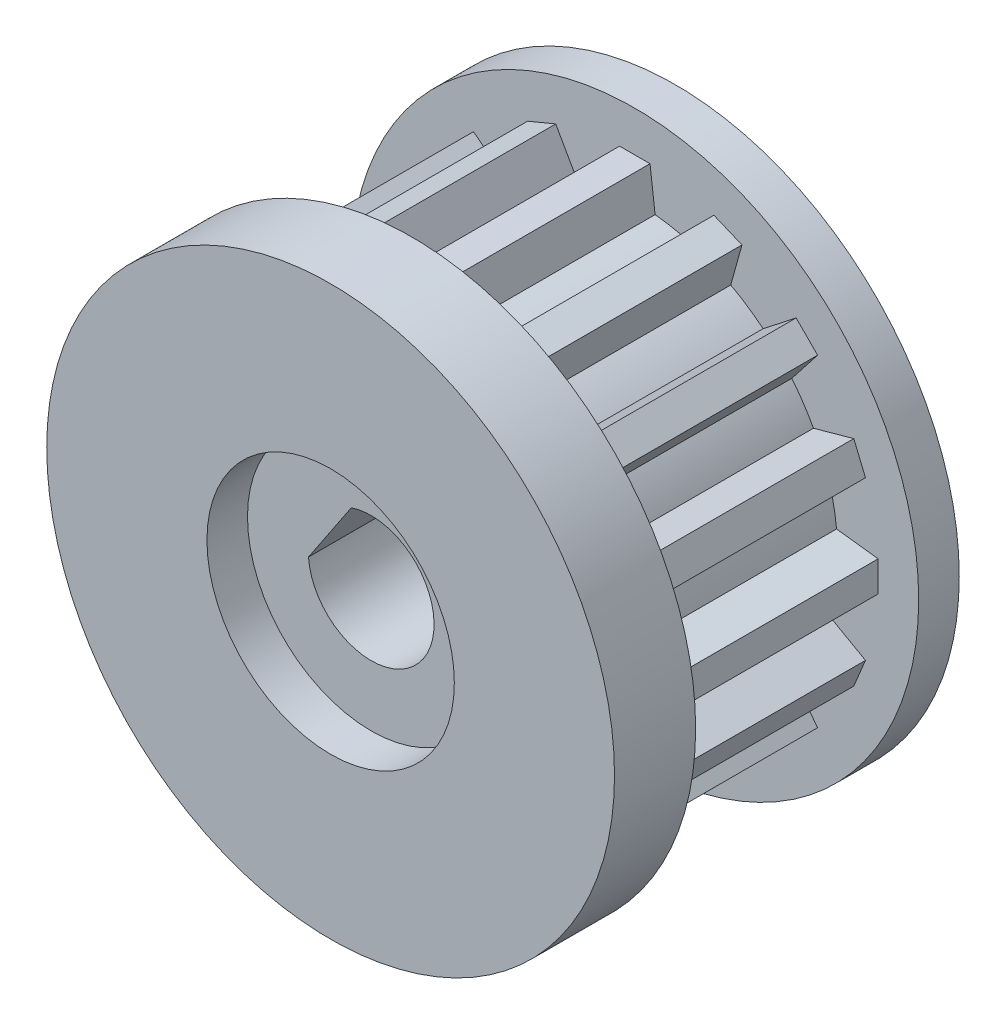
SolidWorks part; units mm, degrees
ref_plane "正面" through (0, 0, 0) normal (0, 0, 1) x (1, 0, 0)
ref_plane "平面" through (0, 0, 0) normal (0, 1, 0) x (1, 0, 0)
ref_plane "右側面" through (0, 0, 0) normal (1, 0, 0) x (0, 0, -1)
sketch "ｽｹｯﾁ1" plane through (0, 0, 0) normal (0, 0, 1) x (1, 0, 0)
  line L0 (-0.75, 12) -> (-1, 9.9499)
  line L1 (-0.75, 12) -> (0.75, 12)
  line L2 (-0.75, 12) -> (-0.75, 8)
  line L3 (-0.75, 8) -> (0.75, 8)
  line L4 (0.75, 12) -> (0.75, 8)
  line L5 (-0.75, 12) -> (0.75, 8) construction
  line L6 (-0.75, 8) -> (0.75, 12) construction
  line L7 (0.75, 12) -> (1, 9.9499)
  line L8 (1, 9.9499) -> (-1, 9.9499)
  line L9 (3.8993, 11.3736) -> (2.8838, 9.5752)
  line L10 (3.8993, 11.3736) -> (5.2851, 10.7995)
  line L11 (5.2851, 10.7995) -> (4.7315, 8.8098)
  line L12 (7.955, 9.0156) -> (6.3285, 7.7427)
  line L13 (7.955, 9.0156) -> (9.0156, 7.955)
  line L14 (9.0156, 7.955) -> (7.7427, 6.3285)
  line L15 (10.7995, 5.2851) -> (8.8098, 4.7315)
  line L16 (10.7995, 5.2851) -> (11.3736, 3.8993)
  line L17 (11.3736, 3.8993) -> (9.5752, 2.8838)
  line L18 (12, 0.75) -> (9.9499, 1)
  line L19 (12, 0.75) -> (12, -0.75)
  line L20 (12, -0.75) -> (9.9499, -1)
  line L21 (11.3736, -3.8993) -> (9.5752, -2.8838)
  line L22 (11.3736, -3.8993) -> (10.7995, -5.2851)
  line L23 (10.7995, -5.2851) -> (8.8098, -4.7315)
  line L24 (9.0156, -7.955) -> (7.7427, -6.3285)
  line L25 (9.0156, -7.955) -> (7.955, -9.0156)
  line L26 (7.955, -9.0156) -> (6.3285, -7.7427)
  line L27 (5.2851, -10.7995) -> (4.7315, -8.8098)
  line L28 (5.2851, -10.7995) -> (3.8993, -11.3736)
  line L29 (3.8993, -11.3736) -> (2.8838, -9.5752)
  line L30 (0.75, -12) -> (1, -9.9499)
  line L31 (0.75, -12) -> (-0.75, -12)
  line L32 (-0.75, -12) -> (-1, -9.9499)
  line L33 (-3.8993, -11.3736) -> (-2.8838, -9.5752)
  line L34 (-3.8993, -11.3736) -> (-5.2851, -10.7995)
  line L35 (-5.2851, -10.7995) -> (-4.7315, -8.8098)
  line L36 (-7.955, -9.0156) -> (-6.3285, -7.7427)
  line L37 (-7.955, -9.0156) -> (-9.0156, -7.955)
  line L38 (-9.0156, -7.955) -> (-7.7427, -6.3285)
  line L39 (-10.7995, -5.2851) -> (-8.8098, -4.7315)
  line L40 (-10.7995, -5.2851) -> (-11.3736, -3.8993)
  line L41 (-11.3736, -3.8993) -> (-9.5752, -2.8838)
  line L42 (-12, -0.75) -> (-9.9499, -1)
  line L43 (-12, -0.75) -> (-12, 0.75)
  line L44 (-12, 0.75) -> (-9.9499, 1)
  line L45 (-11.3736, 3.8993) -> (-9.5752, 2.8838)
  line L46 (-11.3736, 3.8993) -> (-10.7995, 5.2851)
  line L47 (-10.7995, 5.2851) -> (-8.8098, 4.7315)
  line L48 (-9.0156, 7.955) -> (-7.7427, 6.3285)
  line L49 (-9.0156, 7.955) -> (-7.955, 9.0156)
  line L50 (-7.955, 9.0156) -> (-6.3285, 7.7427)
  line L51 (-5.2851, 10.7995) -> (-4.7315, 8.8098)
  line L52 (-5.2851, 10.7995) -> (-3.8993, 11.3736)
  line L53 (-3.8993, 11.3736) -> (-2.8838, 9.5752)
  line L54 (0, 0) -> (1, 9.9499) construction
  line L56 (-6.364, 0) -> (0, -6.364) construction
  line L57 (0, -6.364) -> (6.364, 0) construction
  line L59 (0, 6.364) -> (-6.364, 0) construction
  line L60 (6.364, 0) -> (0, 6.364) construction
  circle A0 centre (0, 0) radius 10
  circle A1 centre (0, 0) radius 3.1
  circle A2 centre (0, 0) radius 4.5 construction
  point P3 (0, 10)
  dimension "D1" = 20
  dimension "D8" = 6.2
  dimension "D2" = 1.5
  dimension "D3" = 2
  dimension "D4" = 0
  dimension "D5" = 2
  dimension "D7" = 10
  dimension "D9" = 9
  dimension "D6" = 16
extrude "ﾎﾞｽ - 押し出し1" add sketch "ｽｹｯﾁ1" along normal blind 11 contours A0 L53 L52 L51 | A0 L2 L0 | A0 L4 L1 L2 | A0 L7 L4 | A0 L50 L49 L48 | A0 L47 L46 L45 | A0 L44 L43 L42 | A0 L41 L40 L39 | A0 L38 L37 L36 | A0 L35 L34 L33 | A0 L32 L31 L30 | A0 L29 L28 L27 | A0 L26 L25 L24 | A0 L23 L22 L21 | A0 L20 L19 L18 | A0 L17 L16 L15 | A0 L14 L13 L12 | A0 L11 L10 L9 | A0 L8 L4 L3 L2 A1 | L4 L8 L2 L3 | L4 A0 L2 L8 | L2 A0 L8 | L8 A0 L4 region at (-0.8333, 10.6409, 0) region at (0, 10.9953, 0) region at (-0.8352, 9.9574, 0) region at (-0.875, 9.6674, 0) region at (0.8333, 10.6409, 0) region at (0, 9.9711, 0) region at (0, 8.9749, 0) region at (-4.1882, 10.1112, 0) region at (0.8352, 9.9574, 0) region at (4.1882, 10.1112, 0) region at (-7.7388, 7.7388, 0) region at (7.7388, 7.7388, 0) region at (-10.1112, 4.1882, 0) region at (10.1112, 4.1882, 0) region at (-10.9443, 0, 0) region at (10.9443, 0, 0) region at (-10.1112, -4.1882, 0) region at (-7.7388, -7.7388, 0) region at (10.1112, -4.1882, 0) region at (-4.1882, -10.1112, 0) region at (7.7388, -7.7388, 0) region at (0, -10.9443, 0) region at (4.1882, -10.1112, 0)
ref_axis "軸1" through (0, 0, 11) along (0, 0, -1)
ref_plane "平面1" through (0, 0, 0) normal (0.8315, -0.5556, 0) x (0, 0, -1)
sketch "ｽｹｯﾁ3" plane through (0, 0, 0) normal (0, 0, -1) x (-1, 0, 0)
  circle A0 centre (0, 0) radius 14
  circle A1 centre (0, 0) radius 3.1
  dimension "D1" = 28
  dimension "D2" = 6.2
extrude "ﾎﾞｽ - 押し出し2" add sketch "ｽｹｯﾁ3" along normal blind 2
sketch "ｽｹｯﾁ4" plane through (0, 0, 11) normal (0, 0, 1) x (1, 0, 0)
  circle A0 centre (0, 0) radius 3.1
  circle A1 centre (0, 0) radius 14
  dimension "D1" = 28
  dimension "D2" = 6.2
extrude "ﾎﾞｽ - 押し出し3" add sketch "ｽｹｯﾁ4" along normal blind 2
sketch "ｽｹｯﾁ5" plane through (0, 0, 13) normal (0, 0, 1) x (1, 0, 0)
  circle A0 centre (0, 0) radius 6.1
  circle M1 centre (0, 0) radius 14
  dimension "D1" = 12.2
extrude "ﾎﾞｽ - 押し出し4" add sketch "ｽｹｯﾁ5" along normal blind 2 contours A0 M1 region at (-13.604, 0, 13)
sketch "ｽｹｯﾁ6" plane through (0, 0, -2) normal (0, 0, -1) x (-1, 0, 0)
  line L0 (0.9811, 2.9407) -> (3.0923, -0.2189)
  line L1 (-3.3612, 5.0304) -> (3.3612, -5.0304) construction
  circle A0 centre (0, 0) radius 3.1 construction
  circle A2 centre (0, 0) radius 3.1
  arc A3 (3.0923, -0.2189) -> (0.9811, 2.9407) centre (0, 0) ccw
  dimension "D1" = 0
  dimension "D2" = 3.8
  dimension "D3" = 0
extrude "ﾎﾞｽ - 押し出し5" add sketch "ｽｹｯﾁ6" against normal up to surface (15 mm away) up to face at (6.1, 0, 13)
sketch "ｽｹｯﾁ2" plane through (0, 0, 0) normal (0.8315, -0.5556, 0) x (0, 0, -1)
  circle A0 centre (-5.5, 0) radius 1.65
  dimension "D1" = 5.5
  dimension "D2" = 3.3
extrude "ｶｯﾄ - 押し出し3" cut sketch "ｽｹｯﾁ2" against normal through all
